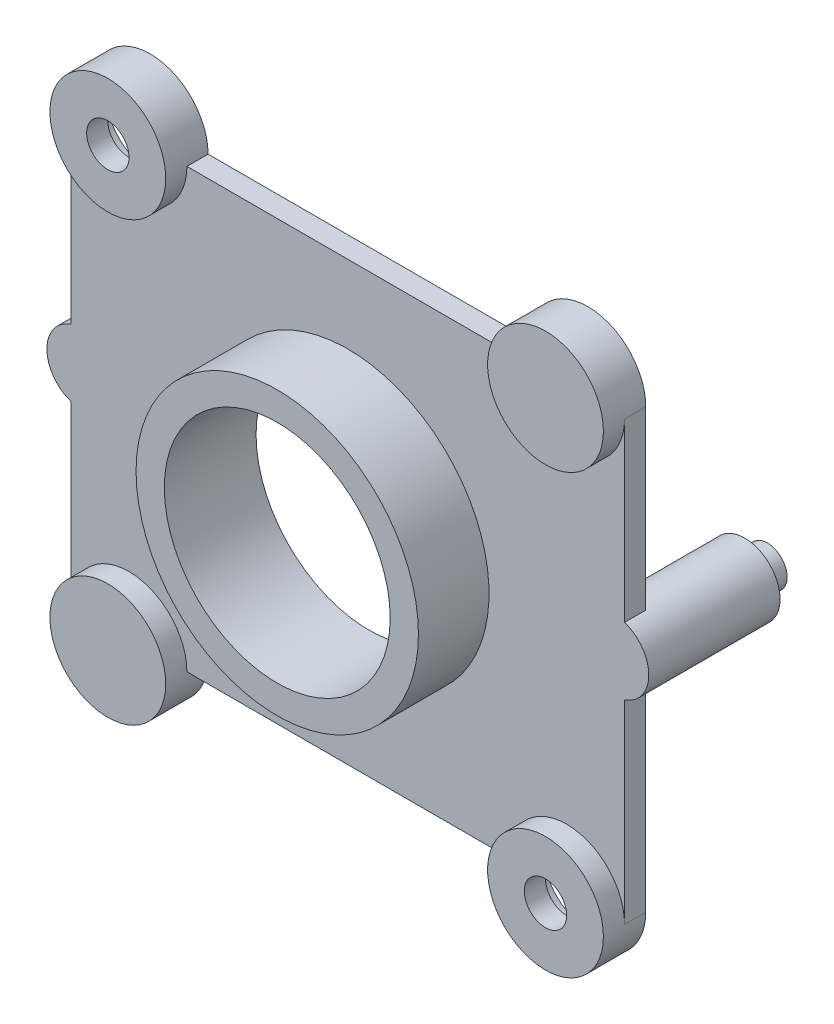
SolidWorks part; units mm, degrees
material "Titanium"
ref_plane "Front Plane" through (0, 0, 0) normal (0, 0, 1) x (1, 0, 0)
ref_plane "Top Plane" through (0, 0, 0) normal (0, 1, 0) x (1, 0, 0)
ref_plane "Right Plane" through (0, 0, 0) normal (1, 0, 0) x (0, 0, -1)
sketch "Sketch1" plane through (0, 0, 0) normal (0, 0, 1) x (1, 0, 0)
  line L0 (-11.4, 15.5) -> (11.4, 15.5)
  line L1 (19.6, 15.5) -> (19.6, -15.5) construction
  line L2 (11.4, -15.5) -> (-11.4, -15.5)
  line L3 (-19.6, -15.5) -> (-19.6, 15.5) construction
  line L4 (-12.4065, -15.3) -> (-18.5935, -15.3)
  line L5 (-31.75, -15.3) -> (26.9875, -15.3) construction
  line L6 (-25.4, 15.3) -> (38.1, 15.3) construction
  line L7 (18.5935, 15.3) -> (12.4065, 15.3)
  line L8 (0, 0) -> (34.925, 0) construction
  line L9 (0, 0) -> (-42.0057, -1.4669) construction
  line L10 (0, 0) -> (0, 28.575) construction
  line L11 (0, 0) -> (37.6269, 1.314) construction
  line L12 (-19.6, -15.5) -> (-19.6, -3.03)
  line L13 (-19.6, 15.5) -> (-19.6, 1.7161)
  line L14 (19.6, 15.5) -> (19.6, 3.03)
  line L15 (19.6, -15.5) -> (19.6, -1.7161)
  circle A0 centre (15.5, -15.5) radius 3.1 construction
  circle A1 centre (-15.5, -15.5) radius 3.1 construction
  circle A2 centre (15.5, 15.5) radius 3.1 construction
  circle A3 centre (-15.5, 15.5) radius 3.1 construction
  circle A4 centre (15.5, 15.5) radius 4.1 construction
  circle A5 centre (15.5, -15.5) radius 4.1 construction
  circle A6 centre (-15.5, 15.5) radius 4.1 construction
  circle A7 centre (-15.5, -15.5) radius 4.1 construction
  arc A8 (18.5935, 15.3) -> (12.4065, 15.3) centre (15.5, 15.5) ccw
  arc A9 (-19.6, 15.5) -> (-11.4, 15.5) centre (-15.5, 15.5) cw
  circle A10 centre (15.5, -15.5) radius 3.1
  arc A11 (11.4, 15.5) -> (19.6, 15.5) centre (15.5, 15.5) cw
  arc A12 (-12.4065, -15.3) -> (-18.5935, -15.3) centre (-15.5, -15.5) cw
  arc A13 (19.6, -15.5) -> (11.4, -15.5) centre (15.5, -15.5) cw
  circle A14 centre (-15.5, 15.5) radius 3.1
  arc A15 (-11.4, -15.5) -> (-19.6, -15.5) centre (-15.5, -15.5) cw
  circle A16 centre (-18.8134, -0.657) radius 2.5 construction
  circle A17 centre (18.8134, 0.657) radius 2.5 construction
  arc A18 (-19.6, 1.7161) -> (-19.6, -3.03) centre (-18.8134, -0.657) ccw
  arc A19 (19.6, 3.03) -> (19.6, -1.7161) centre (18.8134, 0.657) cw
  point P0 (-15.5, -15.5)
  point P1 (-15.5, 15.5)
  point P2 (15.5, 15.5)
  point P3 (15.5, -15.5)
  point P37 (-18.8134, -0.657)
  point P41 (18.8134, 0.657)
  dimension "D8" = 6.2
  dimension "DIA_TOP" = 6.2
  dimension "D9" = 6.2
  dimension "D10" = 6.2
  dimension "D11" = 8.2
  dimension "D12" = 8.2
  dimension "D13" = 8.2
  dimension "D14" = 8.2
  dimension "D1" = 15.5
  dimension "HALF_DIST" = 15.5
  dimension "D2" = 15.5
  dimension "D3" = 15.5
  dimension "D4" = 15.5
  dimension "D5" = 15.5
  dimension "D6" = 15.5
  dimension "D7" = 15.5
  dimension "D15" = 0.2
  dimension "D16" = 0.2
  dimension "D17" = 92
  dimension "D18" = 18.8249
  dimension "DIST_AXIS" = 18.8249
extrude "Extrude1" add sketch "Sketch1" along normal blind 1.5
sketch "Sketch2" plane through (0, 0, 1.5) normal (0, 0, 1) x (1, 0, 0)
  circle A0 centre (-15.5, 15.5) radius 4.1
  circle A1 centre (15.5, 15.5) radius 4.1
  circle A2 centre (15.5, -15.5) radius 4.1
  circle A3 centre (-15.5, -15.5) radius 4.1
  circle A4 centre (-15.5, 15.5) radius 1.5
  circle A5 centre (15.5, -15.5) radius 1.5
extrude "Extrude2" add sketch "Sketch2" along normal blind 1.5
sketch "Sketch3" plane through (0, 0, 0) normal (0, 0, -1) x (-1, 0, 0)
  circle A0 centre (18.8134, -0.657) radius 2.5
  circle A1 centre (-18.8134, 0.657) radius 2.5
extrude "Extrude3" add sketch "Sketch3" along normal blind 7.8
sketch "Sketch4" plane through (0, 0, -7.8) normal (0, 0, -1) x (-1, 0, 0)
  circle A0 centre (-18.8134, 0.657) radius 1.4
  circle A1 centre (18.8134, -0.657) radius 1.4
extrude "Extrude4" add sketch "Sketch4" along normal blind 1.6
sketch "Sketch5" plane through (0, 0, 0) normal (0, 0, -1) x (-1, 0, 0)
  circle A0 centre (0, 0) radius 8
extrude "Extrude5" cut sketch "Sketch5" against normal through all
sketch "Sketch6" plane through (0, 0, 1.5) normal (0, 0, 1) x (1, 0, 0)
  circle A0 centre (0, 0) radius 8
  circle A1 centre (0, 0) radius 10
extrude "Extrude6" add sketch "Sketch6" along normal blind 5
equation "\"D2@Sketch1\" = \"HALF_DIST\""
equation "\"D3@Sketch1\" = \"HALF_DIST\""
equation "\"D1@Sketch1\" = \"HALF_DIST\""
equation "\"D4@Sketch1\" = \"HALF_DIST\""
equation "\"D5@Sketch1\" = \"HALF_DIST\""
equation "\"D6@Sketch1\" = \"HALF_DIST\""
equation "\"D7@Sketch1\" = \"HALF_DIST\""
equation "\"D8@Sketch1\" = \"DIA_TOP\""
equation "\"D9@Sketch1\" = \"DIA_TOP\""
equation "\"D10@Sketch1\" = \"DIA_TOP\""
equation "\"D11@Sketch1\" = \"DIA_TOP\"+2"
equation "\"D12@Sketch1\" = \"DIA_TOP\"+2"
equation "\"D13@Sketch1\" = \"DIA_TOP\"+2"
equation "\"D14@Sketch1\" = \"DIA_TOP\"+2"
equation "\"D18@Sketch1\" = \"DIST_AXIS\""
